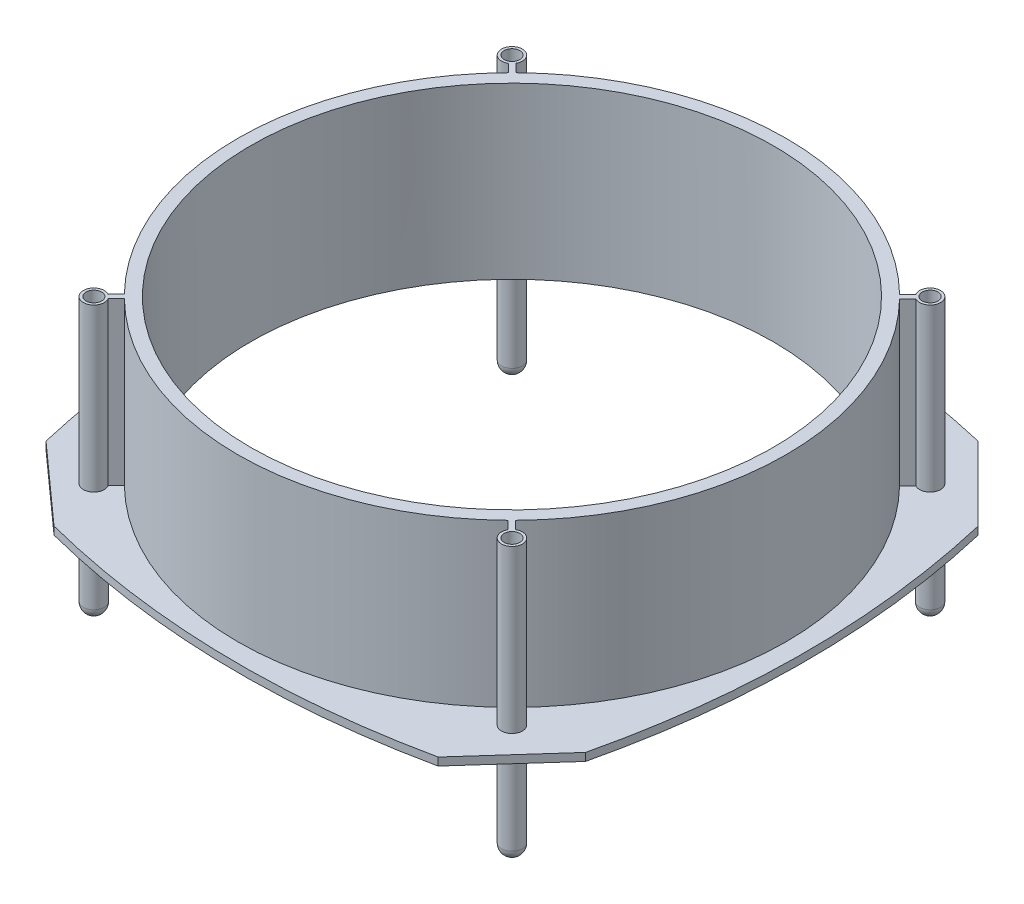
SolidWorks part; units mm, degrees
ref_plane "Front Plane" through (0, 0, 0) normal (0, 0, 1) x (1, 0, 0)
ref_plane "Top Plane" through (0, 0, 0) normal (0, 1, 0) x (1, 0, 0)
ref_plane "Right Plane" through (0, 0, 0) normal (1, 0, 0) x (0, 0, -1)
sketch "Sketch2" plane through (0, 0, 0) normal (0, 1, 0) x (1, 0, 0)
  line L0 (3824.4294, -5236.7276) -> (5157.6927, -3749.6242)
  line L2 (5163.9685, 3752.3444) -> (3751.2089, 5164.1439)
  line L4 (-3751.7702, 5163.5828) -> (-5163.7079, 3750.9614)
  line L6 (-5163.0762, -3751.9198) -> (-3675.9728, -5085.183)
  circle A0 centre (0, 0) radius 5000
  spline S0 degree 2 poles (-3751.7702, 5163.5828) (-0.3376, 6037.3855) (3751.2089, 5164.1439) knots 0 0 0 1 1 1
  spline S1 degree 2 poles (-5163.7079, 3750.9614) (-6037.5496, -0.539) (-5163.0762, -3751.9198) knots 0 0 0 1 1 1
  spline S2 degree 2 poles (-3675.9728, -5085.183) (54.6713, -6041.0227) (3824.4294, -5236.7276) knots 0 0 0 1 1 1
  spline S3 degree 2 poles (5163.9685, 3752.3444) (6040.8667, 0.5969) (5157.6927, -3749.6242) knots 0 0 0 1 1 1
extrude "Boss-Extrude2" add sketch "Sketch2" along normal blind 150
sketch "Sketch3" plane through (0, 0, 0) normal (0, 1, 0) x (1, 0, 0)
  circle A0 centre (0, 0) radius 5244.2465
extrude "Boss-Extrude3" add sketch "Sketch3" along normal blind 3250
sketch "Sketch7" plane through (0, 0, 0) normal (0, -1, 0) x (-1, 0, 0)
  circle A0 centre (40, 40) radius 2
sketch "Sketch9" plane through (0, 0, 0) normal (0, -1, 0) x (-1, 0, 0)
  circle A0 centre (4000, 4000) radius 200
extrude "Boss-Extrude12" add sketch "Sketch7" against normal blind 3250 contours A0
extrude "Boss-Extrude13" add sketch "Sketch9" along normal blind 2000 contours A0
fillet "Fillet1" radius 200 2 edges at (-4000, 0, -4200) (-4000, -2000, -4200)
ref_axis "Axis1" through (0, 3512.5, 0) along (0, -1, 0)
pattern_circular "CirPattern7" count 4 over 360 about axis through (0, 3512.5, 0) along (0, -1, 0) of "Boss-Extrude13", "Fillet1"
scale "Scale2" scale about origin uniform scaling yes scale factor 0.01
sketch "Sketch14" plane through (0, 32.5, 0) normal (0, 1, 0) x (1, 0, 0)
  circle A0 centre (0, 0) radius 50
extrude "Cut-Extrude4" cut sketch "Sketch14" against normal through all
extrude "Boss-Extrude14" add sketch "Sketch7<6>" against normal blind 32.5 contours A0
sketch "Sketch7<6>" plane through (0, 0, 0) normal (0, -1, 0) x (-1, 0, 0) same geometry as "Sketch7"
sketch "Sketch15" plane through (0, 32.5, 0) normal (0, 1, 0) x (1, 0, 0)
  circle A0 centre (-40, 40) radius 1.5
  point P2 (-39.9474, 39.9795)
  point P3 (0, 0)
  point P4 (-40.0201, 39.9799)
  point P5 (0, 0)
sketch "Sketch16" plane through (0, 1.5, 0) normal (0, 1, 0) x (1, 0, 0)
  line L0 (-38.2629, 39.0088) -> (-36.6878, 37.4729)
  line L1 (-39.0106, 38.2619) -> (-37.4356, 36.7259)
  circle A0 centre (-40, 40) radius 2 construction
  circle A1 centre (0, 0) radius 52.4425 construction
extrude "Extrude-Thin10" add sketch "Sketch16" along normal blind 31 thin contours L0 thin type one direction wall 1
extrude "Cut-Extrude5" cut sketch "Sketch15" against normal blind 7.5 contours A0
pattern_circular "CirPattern1" count 4 over 360 about axis through (0, 3512.5, 0) along (0, -1, 0) of "Boss-Extrude14", "Cut-Extrude5", "Extrude-Thin10"
